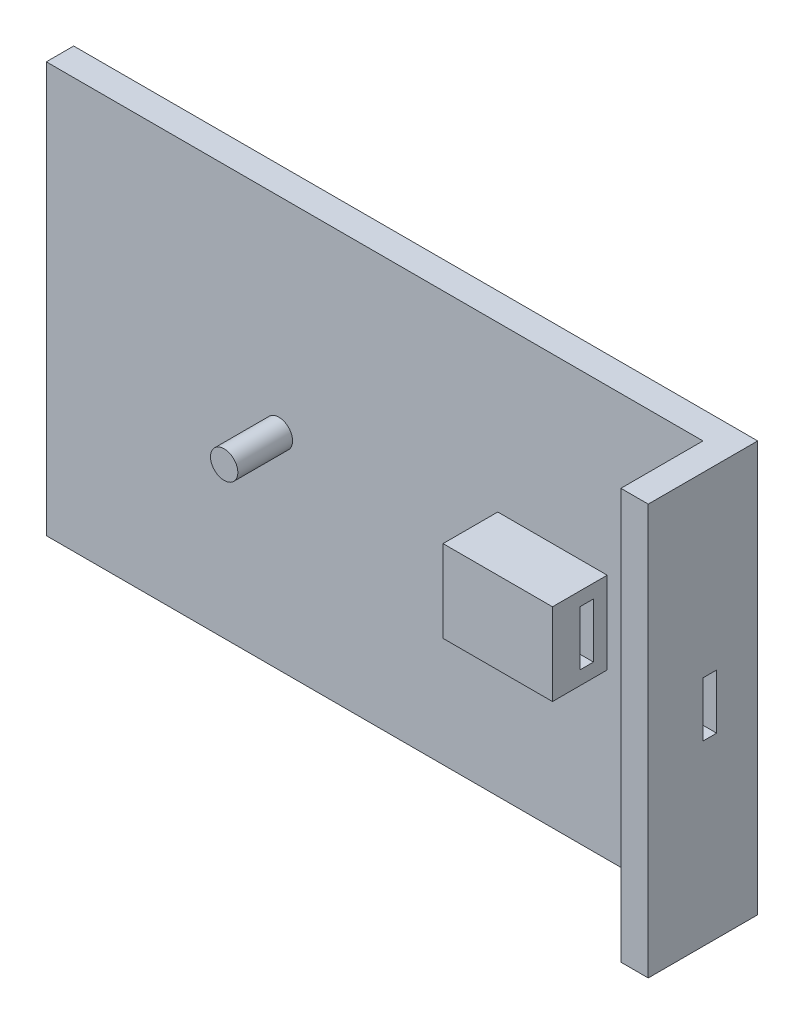
SolidWorks part; units mm, degrees
note: The reader was unsure of these and kept them because the rebuilt part matched: shared geometry of "Sketch1<5>", "Sketch1<6>", "Sketch1<7>".
ref_plane "Front Plane" through (0, 0, 0) normal (0, 0, 1) x (1, 0, 0)
ref_plane "Top Plane" through (0, 0, 0) normal (0, 1, 0) x (1, 0, 0)
ref_plane "Right Plane" through (0, 0, 0) normal (1, 0, 0) x (0, 0, -1)
sketch "Sketch1" plane through (0, 0, 0) normal (0, 0, 1) x (1, 0, 0)
  line L0 (115, 75) -> (115, -75)
  line L1 (-125, 75) -> (125, 75)
  line L2 (-125, 75) -> (-125, -75)
  line L3 (-125, -75) -> (125, -75)
  line L4 (125, 75) -> (125, -75)
  line L5 (40, -10) -> (80, -10)
  line L7 (0, 75) -> (0, -75) construction
  line L11 (40, 10) -> (80, 10)
  line L15 (80, 15) -> (80, 10)
  line L16 (40, 15) -> (40, 10)
  line L17 (40, 15) -> (80, 15)
  line L18 (40, -15) -> (80, -15)
  line L19 (40, 75) -> (40, -75) construction
  line L20 (80, 75) -> (80, -75) construction
  line L21 (80, -10) -> (80, -15)
  line L23 (40, -10) -> (40, -15)
  circle A0 centre (-40, 0) radius 5
  point P0 (0, 0)
  dimension "D1" = 10
  dimension "D5" = 80
  dimension "D6" = 40
  dimension "D7" = 5
  dimension "D8" = 5
extrude "Boss-Extrude1" add sketch "Sketch1" along normal blind 10
extrude "Boss-Extrude2" add sketch "Sketch1<5>" along normal blind 40 contours L4 L1 L0 L3
sketch "Sketch1<5>" plane through (0, 0, 0) normal (0, 0, 1) x (1, 0, 0) same geometry as "Sketch1"
extrude "Boss-Extrude3" add sketch "Sketch1<6>" along normal blind 30
sketch "Sketch1<6>" plane through (0, 0, 0) normal (0, 0, 1) x (1, 0, 0) same geometry as "Sketch1"
extrude "Boss-Extrude4" add sketch "Sketch1<7>" along normal blind 30 contours L17 L15 L11 L16 | L18 L21 L5 L23
sketch "Sketch1<7>" plane through (0, 0, 0) normal (0, 0, 1) x (1, 0, 0) same geometry as "Sketch1"
sketch "Sketch6" plane through (40, 0, 0) normal (-1, 0, 0) x (0, 0, 1)
  line L0 (30, -10) -> (10, -10) construction
  line L1 (10, 10) -> (15, 10)
  line L2 (10, 10) -> (10, -10)
  line L3 (10, -10) -> (15, -10)
  line L4 (15, 10) -> (15, -10)
  line L5 (20, 10) -> (30, 10)
  line L6 (20, 10) -> (20, -10.2188)
  line L7 (30, 10) -> (30, -10.2188)
  line L8 (20, -10.2188) -> (30, -10.2188)
  line L9 (30, 10) -> (10, 10) construction
extrude "Boss-Extrude5" add sketch "Sketch6" against normal up to surface (40 mm away) up to face at (80, 12.5, 20)
sketch "Sketch7" plane through (115, 0, 0) normal (-1, 0, 0) x (0, 0, 1)
  line L1 (15, 10) -> (20, 10)
  line L2 (15, 10) -> (15, -10)
  line L3 (15, -10) -> (20, -10)
  line L4 (20, 10) -> (20, -10)
extrude "Cut-Extrude1" cut sketch "Sketch7" against normal up to surface (10 mm away) up to face at (125, 0, 20)
